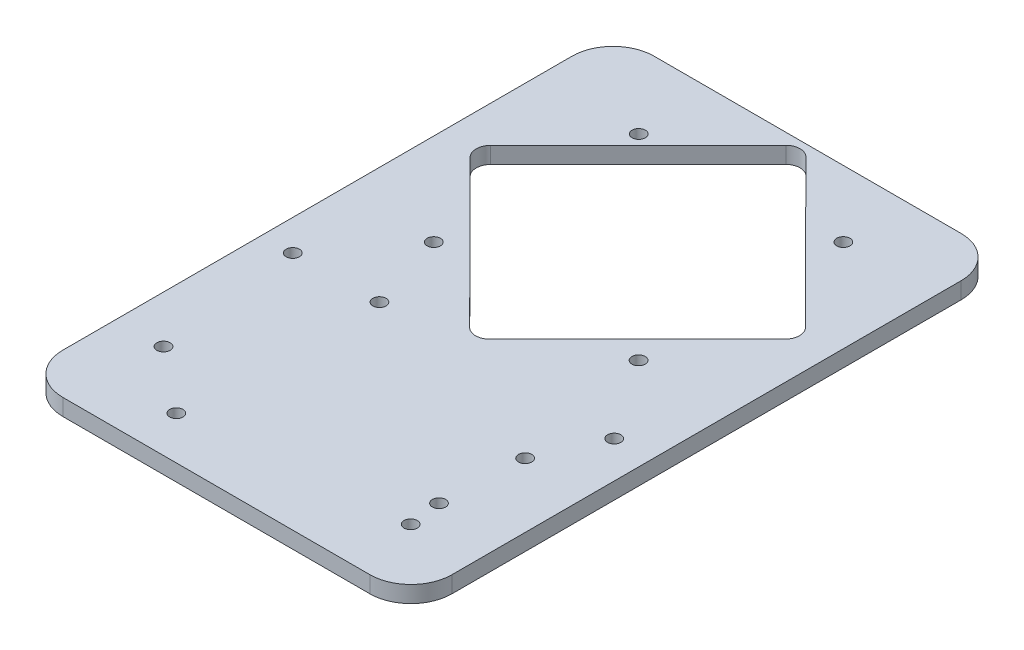
SolidWorks part; units mm, degrees
material "Acrylic (Medium-high impact)"
ref_plane "Front Plane" through (0, 0, 0) normal (0, 0, 1) x (1, 0, 0)
ref_plane "Top Plane" through (0, 0, 0) normal (0, 1, 0) x (1, 0, 0)
ref_plane "Right Plane" through (0, 0, 0) normal (1, 0, 0) x (0, 0, -1)
sketch "Sketch1" plane through (0, 0, 0) normal (0, 1, 0) x (1, 0, 0)
  line L0 (-175.9156, 142.6571) -> (-117.135, 142.6608)
  line L1 (-109.2976, 134.8092) -> (-109.2976, 37.3705)
  line L2 (-176.7986, 112.2097) -> (-148.5316, 140.4928)
  line L8 (-183.7531, 37.367) -> (-183.7532, 37.2565)
  line L9 (-175.9156, 29.519) -> (-117.1491, 29.519)
  line L10 (-183.7531, 134.8055) -> (-183.7531, 37.367)
  line L16 (-176.8012, 108.3505) -> (-148.5692, 80.0323)
  line L17 (-144.7168, 80.0299) -> (-116.45, 108.313)
  line L18 (-116.3523, 112.0717) -> (-116.4476, 112.1722)
  line L19 (-116.4476, 112.1722) -> (-144.6796, 140.4904)
  arc A0 (-183.7531, 134.8055) -> (-175.9156, 142.6571) centre (-175.9016, 134.8055) cw
  arc A1 (-117.135, 142.6608) -> (-109.2976, 134.8092) centre (-117.135, 134.8233) cw
  arc A2 (-109.2976, 37.3705) -> (-117.1491, 29.519) centre (-117.1491, 37.3705) cw
  arc A3 (-175.9156, 29.519) -> (-183.7531, 37.367) centre (-175.9156, 37.3565) cw
  arc A4 (-176.7986, 112.2097) -> (-176.8012, 108.3505) centre (-174.7341, 110.2787) ccw
  arc A5 (-148.5692, 80.0323) -> (-144.7168, 80.0299) centre (-146.6418, 81.9538) ccw
  arc A6 (-116.45, 108.313) -> (-116.4476, 112.1722) centre (-118.3819, 110.2438) ccw
  arc A7 (-144.6796, 140.4904) -> (-148.5316, 140.4928) centre (-146.6068, 138.5691) ccw
  circle A8 centre (-162.4353, 37.7632) radius 1.27
  circle A9 centre (-121.6023, 41.7674) radius 1.27
  circle A10 centre (-122.3798, 47.9761) radius 1.27
  circle A11 centre (-174.7181, 47.5835) radius 1.27
  circle A12 centre (-177.8531, 75.4567) radius 1.27
  circle A13 centre (-161.4165, 75.6081) radius 1.27
  circle A14 centre (-121.6023, 63.6734) radius 1.27
  circle A15 centre (-116.3294, 75.4567) radius 1.27
  circle A16 centre (-126.973, 90.7615) radius 1.27
  circle A17 centre (-166.1599, 90.7612) radius 1.27
  circle A18 centre (-164.473, 128.292) radius 1.27
  circle A19 centre (-126.973, 129.9578) radius 1.27
  point P8 (-164.473, 128.292)
  point P9 (-126.973, 129.9578)
  point P10 (-126.973, 90.7615)
  point P11 (-166.1599, 90.7612)
  point P12 (-177.8531, 75.4567)
  point P13 (-161.4165, 75.6081)
  point P14 (-116.3294, 75.4567)
  point P15 (-121.6023, 63.6734)
  point P16 (-174.7181, 47.5835)
  point P17 (-162.4353, 37.7632)
  point P18 (-121.6023, 41.7674)
  point P19 (-122.3798, 47.9761)
  dimension "D1" = 2.54
extrude "Boss-Extrude2" add sketch "Sketch1" along normal blind 3.175 contours A3 L9 A2 L1 A1 L0 A0 L10 A19 A18 A17 A16 A15 A14 A13 A12 A11 A10 A9 A8 A7 L19 A6 L17 A5 L16 A4 L2 region at (-146.5054, 0, -78.2347)
